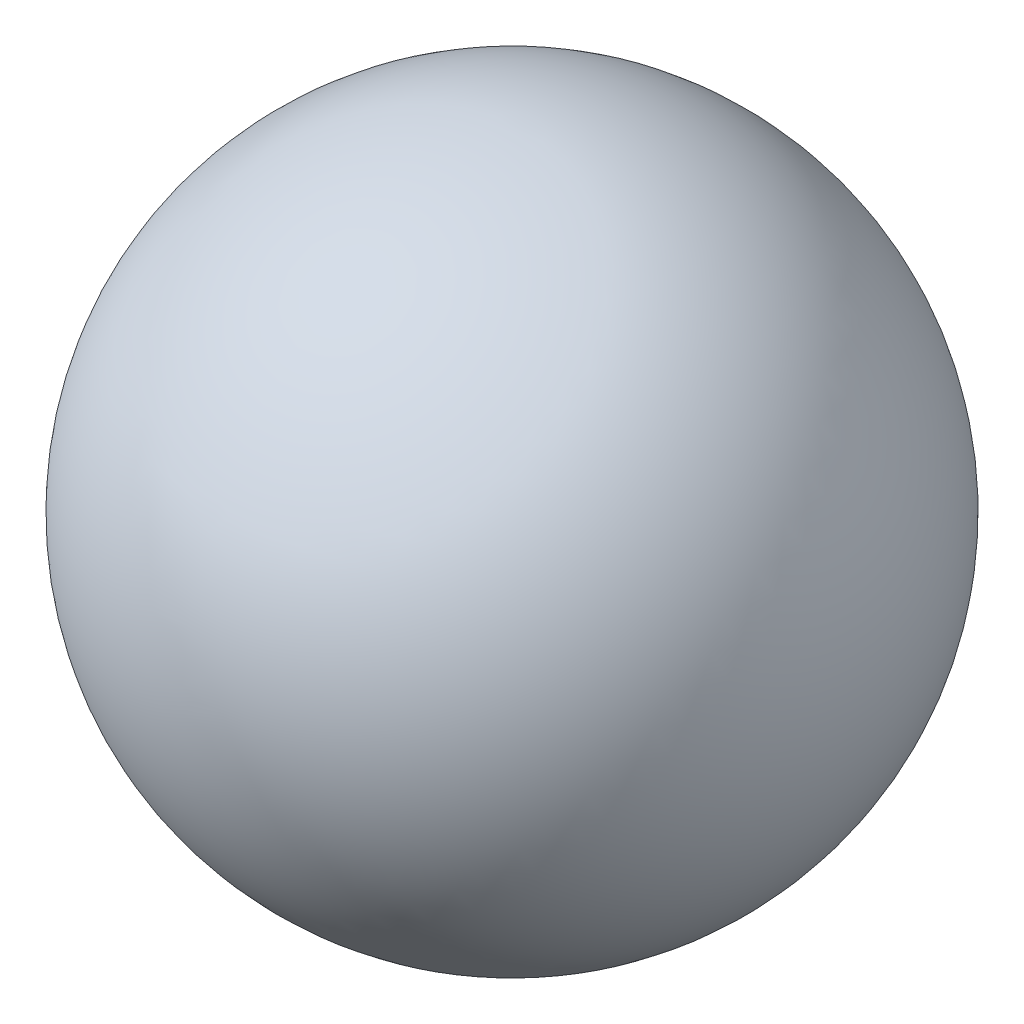
SolidWorks part; units mm, degrees
ref_plane "Front Plane" through (0, 0, 0) normal (0, 0, 1) x (1, 0, 0)
ref_plane "Top Plane" through (0, 0, 0) normal (0, 1, 0) x (1, 0, 0)
ref_plane "Right Plane" through (0, 0, 0) normal (1, 0, 0) x (0, 0, -1)
sketch "Sketch1" plane through (0, 0, 0) normal (0, 1, 0) x (1, 0, 0)
  line L0 (0, 95) -> (0, -95)
  arc A1 (0, 95) -> (0, -95) centre (0, 0) ccw
  dimension "D1" = 190
revolve "Revolve3" add sketch "Sketch1" angle 360 about L0
sketch "Sketch2" plane through (0, 0, 0) normal (0, 1, 0) x (1, 0, 0)
  circle A0 centre (0, 0) radius 5
  dimension "D1" = 10
extrude "Boss-Extrude1" add sketch "Sketch2" against normal blind 95
